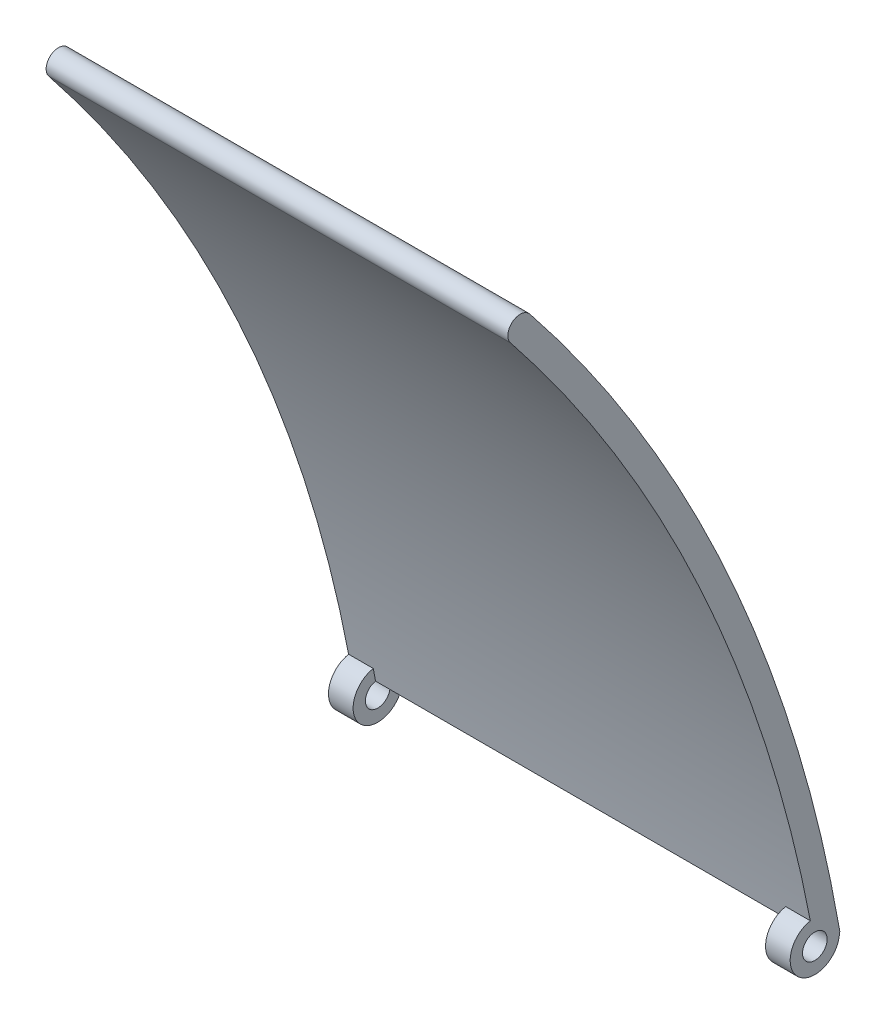
SolidWorks part; units mm, degrees
ref_plane "Front Plane" through (0, 0, 0) normal (0, 0, 1) x (1, 0, 0)
ref_plane "Top Plane" through (0, 0, 0) normal (0, 1, 0) x (1, 0, 0)
ref_plane "Right Plane" through (0, 0, 0) normal (1, 0, 0) x (0, 0, -1)
sketch "Sketch9" plane through (0, 0, 0) normal (1, 0, 0) x (0, 0, -1)
  line L0 (0, 0) -> (-50000, 0) construction
  line L1 (0, 0) -> (0, 50000) construction
  line L2 (0, 0) -> (-0.1736, 0.9848)
  line L3 (-5.0771, 0) -> (-5.0977, 0.1166)
  line L4 (0, 0) -> (-5.0771, 0)
  line L7 (-4.924, -0.8682) -> (-5.0977, 0.1166) construction
  arc A0 (-0.1736, 0.9848) -> (-62.9066, 140) centre (-304.4663, -52.6702) ccw
  arc A1 (-5.0977, 0.1166) -> (-66.8155, 136.8822) centre (-304.4663, -52.6702) ccw
  arc A2 (-66.8155, 136.8822) -> (-62.9066, 140) centre (-64.8611, 138.4411) cw
  dimension "D1" = 10
  dimension "D2" = 1
  dimension "D3" = 140
  dimension "D5" = 66.8155
  dimension "D4" = 5
extrude "Boss-Extrude8" add sketch "Sketch9" along normal mid plane 93.68
sketch "Sketch10" plane through (46.84, 0, 0) normal (1, 0, 0) x (0, 0, -1)
  circle A0 centre (-5.0771, 0) radius 5
  dimension "D1" = 10
extrude "Boss-Extrude9" add sketch "Sketch10" against normal blind 5
mirror "Mirror1" about plane through (0, 0, 0) normal (1, 0, 0) of "Boss-Extrude9"
sketch "Sketch11" plane through (46.84, 0, 0) normal (1, 0, 0) x (0, 0, -1)
  circle A1 centre (-5.0771, 0) radius 2.5
  dimension "D1" = 5
extrude "Cut-Extrude4" cut sketch "Sketch11" against normal through all
sketch "Sketch13" plane through (46.84, 0, 0) normal (1, 0, 0) x (0, 0, -1)
  line L0 (-10.0771, 0) -> (-67.3611, 0)
  line L1 (-67.3611, 0) -> (-67.3611, 138.4411)
  line L2 (-64.8611, 138.4411) -> (-67.3611, 138.4411) construction
  line L3 (-5.0771, 0) -> (49994.9229, 0) construction
  arc A0 (-5.9839, 4.9171) -> (-0.0771, 0) centre (-5.0771, 0) ccw construction
  arc A1 (-5.9839, 4.9171) -> (-10.0771, 0) centre (-5.0771, 0) ccw
  arc A2 (-67.3611, 138.4411) -> (-66.8155, 136.8822) centre (-64.8611, 138.4411) ccw
  arc A3 (-5.9839, 4.9171) -> (-66.8155, 136.8822) centre (-304.4663, -52.6702) ccw
  arc A4 (-5.9839, 4.9171) -> (-66.8155, 136.8822) centre (-304.4663, -52.6702) ccw construction
  arc A7 (-62.9066, 140) -> (-66.8155, 136.8822) centre (-64.8611, 138.4411) ccw construction
  point P28 (-28.3986, 74.5879)
  dimension "D1" = 90
